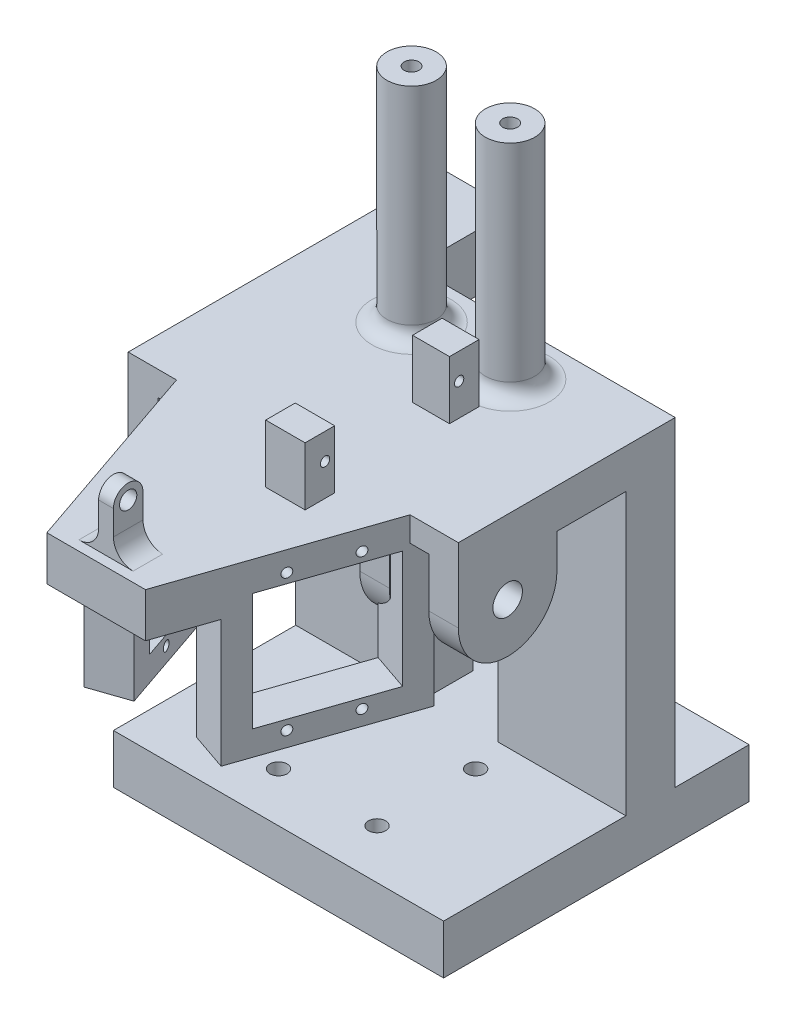
SolidWorks part; units mm, degrees
ref_plane "前视基准面" through (0, 0, 0) normal (0, 0, 1) x (1, 0, 0)
ref_plane "上视基准面" through (0, 0, 0) normal (0, 1, 0) x (1, 0, 0)
ref_plane "右视基准面" through (0, 0, 0) normal (1, 0, 0) x (0, 0, -1)
sketch "草图1" plane through (0, 0, 0) normal (0, 1, 0) x (1, 0, 0)
  line L1 (-33.5, 31) -> (33.5, 31)
  line L2 (-33.5, 31) -> (-33.5, -31)
  line L3 (-33.5, -31) -> (33.5, -31)
  line L4 (33.5, 31) -> (33.5, -31)
  line L5 (-33.5, 31) -> (33.5, -31) construction
  line L6 (-33.5, -31) -> (33.5, 31) construction
  point P0 (0, 0)
  dimension "D1" = 62
  dimension "D2" = 67
extrude "凸台-拉伸1" add sketch "草图1" along normal blind 10
sketch "草图3" plane through (0, 10, 0) normal (0, 1, 0) x (1, 0, 0)
  line L0 (-33.5, 31) -> (-33.5, -31) construction
  line L1 (-33.5, 36) -> (-19.5, 36)
  line L2 (-33.5, 36) -> (-33.5, 16)
  line L3 (-33.5, 16) -> (-19.5, 16)
  line L4 (-19.5, 36) -> (-19.5, 16)
  line L5 (33.5, 31) -> (-33.5, 31) construction
  dimension "D1" = 20
  dimension "D2" = 5
  dimension "D3" = 19.5
extrude "凸台-拉伸2" add sketch "草图3" along normal blind 12.5
sketch "草图4" plane through (-33.5, 0, 0) normal (-1, 0, 0) x (0, 0, 1)
  line L1 (-16, 10) -> (-6, 10)
  line L2 (-16, 10) -> (-16, 75)
  line L3 (-16, 75) -> (-6, 75)
  line L4 (-6, 10) -> (-6, 75)
  dimension "D1" = 10
  dimension "D2" = 65
extrude "凸台-拉伸3" add sketch "草图4" against normal blind 67
sketch "草图5" plane through (0, 75, 0) normal (0, 1, 0) x (1, 0, 0)
  line L0 (33.5, -31) -> (33.5, 6) construction
  line L1 (-33.5, 16) -> (33.5, 16)
  line L2 (-33.5, 16) -> (-33.5, -28)
  line L3 (-33.5, -28) -> (33.5, -28)
  line L4 (33.5, 16) -> (33.5, -28)
  dimension "D1" = 44
extrude "凸台-拉伸4" add sketch "草图5" against normal blind 8
sketch "草图6" plane through (33.5, 0, 0) normal (1, 0, 0) x (0, 0, -1)
  line L0 (6, 10) -> (6, 67) construction
  line L1 (-28, 75) -> (16, 75) construction
  line L2 (-28, 60) -> (-28, 67)
  line L3 (-28, 67) -> (6, 67) construction
  line L5 (-28, 67) -> (-8, 67)
  line L6 (-8, 67) -> (-8, 60)
  arc A0 (-28, 60) -> (-8, 60) centre (-18, 60) ccw
  dimension "D1" = 24
  dimension "D2" = 15
  dimension "D3" = 20
extrude "凸台-拉伸5" add sketch "草图6" against normal blind 20
sketch "草图7" plane through (33.5, 0, 0) normal (1, 0, 0) x (0, 0, -1)
  line L0 (-28, 60) -> (-28, 70.0002)
  line L1 (-28, 60) -> (-28, 75) construction
  line L2 (-28, 70.0002) -> (-8, 70.0002)
  line L3 (-8, 70.0002) -> (-8, 60)
  arc A0 (-28, 60) -> (-8, 60) centre (-18, 60) ccw construction
  arc A1 (-28, 60) -> (-8, 60) centre (-18, 60) ccw
extrude "切除-拉伸1" cut sketch "草图7" against normal blind 8 from offset 6 offset against normal yes
sketch "草图8" plane through (0, 75, 0) normal (0, 1, 0) x (1, 0, 0)
  line L0 (0, -68) -> (10, -68)
  line L2 (10, -68) -> (23.6942, -28)
  line L3 (23.6942, -28) -> (0, -28)
  line L4 (0, -28) -> (0, -68)
  line L5 (-33.5, -28) -> (33.5, -28) construction
  dimension "D1" = 10
  dimension "D2" = 40
extrude "凸台-拉伸6" add sketch "草图8" against normal blind 6
sketch "草图9" plane through (33.5, 0, 0) normal (1, 0, 0) x (0, 0, -1)
  circle A0 centre (-18, 60) radius 3
  dimension "D1" = 6
extrude "切除-拉伸2" cut sketch "草图9" against normal blind 23
sketch "草图10" plane through (29.7887, 0, 10.1983) normal (0.9461, 0, 0.3239) x (0.3239, 0, -0.9461)
  line L1 (-44, 75) -> (-15, 75)
  line L4 (-15, 75) -> (-15, 40.2)
  line L5 (-15, 40.2) -> (-43, 40.2)
  line L9 (-44, 45.2) -> (-20, 45.2)
  line L10 (-20, 45.2) -> (-20, 69)
  line L11 (-20, 69) -> (-44, 69)
  line L12 (-61.0952, 75) -> (-18.816, 75) construction
  line L14 (-44, 75) -> (-49, 75)
  line L15 (-61.0952, 75) -> (-18.816, 75) construction
  line L16 (-44, 69) -> (-44, 45.2)
  line L17 (-43, 40.2) -> (-49, 40.2)
  line L18 (-49, 75) -> (-49, 40.2)
  dimension "D1" = 5
  dimension "D2" = 5
  dimension "D3" = 29
  dimension "D4" = 15
  dimension "D5" = 24
  dimension "D6" = 28
  dimension "D7" = 5
  dimension "D8" = 6
  dimension "D9" = 23.8
extrude "凸台-拉伸7" add sketch "草图10" against normal blind 8
sketch "草图12" plane through (0, 75, 0) normal (0, 1, 0) x (1, 0, 0)
  line L1 (-33.5, 36) -> (-19.5, 36)
  line L2 (-33.5, 36) -> (-33.5, 16)
  line L3 (-33.5, 16) -> (-19.5, 16)
  line L4 (-19.5, 36) -> (-19.5, 16)
extrude "凸台-拉伸8" add sketch "草图12" against normal blind 11.5
sketch "草图13" plane through (22.22, 0, 7.6071) normal (-0.9461, 0, -0.3239) x (-0.3239, 0, 0.9461)
  line L0 (61.0952, 69) -> (49, 69) construction
  line L7 (20, 69) -> (20, 45.2) construction
  line L8 (20, 45.2) -> (44, 45.2) construction
  circle A0 centre (38.5, 70.95) radius 0.95
  circle A1 centre (26.5, 70.95) radius 0.95
  circle A2 centre (26.5, 43.25) radius 0.95
  circle A3 centre (38.5, 43.25) radius 0.95
  dimension "D2" = 6.5
  dimension "D3" = 1.95
  dimension "D4" = 1.95
  dimension "D5" = 12
  dimension "D6" = 1.9
  dimension "D7" = 1.9
  dimension "D13" = 1.9
  dimension "D14" = 1.9
extrude "切除-拉伸4" cut sketch "草图13" against normal up to surface (8 mm away) up to face at (18.1355, 63.5501, 44.2366)
sketch "草图14" plane through (0, 75, 0) normal (0, 1, 0) x (1, 0, 0)
  line L0 (33.5, 6) -> (-33.5, 6) construction
  line L1 (4.2, -2) -> (11.7, -2)
  line L2 (4.2, -2) -> (4.2, -8)
  line L3 (4.2, -8) -> (11.7, -8)
  line L4 (11.7, -2) -> (11.7, -8)
  line L5 (12.2, -31.8) -> (12.2, -37.8)
  line L6 (4.2, -37.8) -> (12.2, -37.8)
  line L7 (4.2, -31.8) -> (4.2, -37.8)
  line L8 (4.2, -31.8) -> (12.2, -31.8)
  dimension "D1" = 11.7
  dimension "D2" = 4.2
  dimension "D3" = 6
  dimension "D4" = 14
  dimension "D5" = 6
  dimension "D6" = 8
  dimension "D7" = 23.8
extrude "凸台-拉伸9" add sketch "草图14" along normal blind 11.8
sketch "草图15" plane through (4.2, 0, 0) normal (-1, 0, 0) x (0, 0, 1)
  line L0 (8, 86.8) -> (8, 75) construction
  line L1 (28, 75) -> (-36, 75) construction
  line L2 (31.8, 75) -> (37.8, 75) construction
  line L3 (31.8, 86.8) -> (31.8, 75) construction
  circle A0 centre (33.75, 81.5) radius 0.95
  circle A1 centre (6.05, 81.5) radius 0.95
  dimension "D1" = 1.95
  dimension "D2" = 1.95
  dimension "D3" = 1.9
  dimension "D4" = 1.9
  dimension "D5" = 6.5
  dimension "D6" = 6.5
extrude "切除-拉伸5" cut sketch "草图15" against normal blind 11.8
sketch "草图16" plane through (0, 75, 0) normal (0, 1, 0) x (1, 0, 0)
  line L1 (-1.5, -60) -> (1.5, -60)
  line L2 (-1.5, -60) -> (-1.5, -66)
  line L3 (-1.5, -66) -> (1.5, -66)
  line L4 (1.5, -60) -> (1.5, -66)
  point P4 (0, -66)
  dimension "D2" = 6
  dimension "D3" = 3
  dimension "D4" = 60
extrude "凸台-拉伸10" add sketch "草图16" along normal blind 12
fillet "圆角1" 2 edges at (0, 87, 66) (0, 87, 60) type full round first side face at (0, 79.8, 66) second side face at (0, 79.8, 60) middle face at (0, 87, 63)
sketch "草图17" plane through (-1.5, 0, 0) normal (-1, 0, 0) x (0, 0, 1)
  circle A0 centre (63, 84) radius 1.75
  arc A1 (66, 84) -> (60, 84) centre (63, 84) ccw construction
  dimension "D1" = 3.5
extrude "切除-拉伸6" cut sketch "草图17" against normal blind 7
sketch "草图18" plane through (0, 75, 0) normal (0, 1, 0) x (1, 0, 0)
  line L0 (33.5, 16) -> (-19.5, 16) construction
  circle A0 centre (10, 6) radius 5
  dimension "D1" = 10
  dimension "D2" = 10
  dimension "D3" = 10
extrude "凸台-拉伸11" add sketch "草图18" along normal blind 45
fillet "圆角2" radius 3 1 edges at (10, 75, -1)
mirror "镜向1" about plane through (0, 0, 0) normal (1, 0, 0) of "圆角2", "凸台-拉伸11", "切除-拉伸4", "凸台-拉伸7", "切除-拉伸2", "凸台-拉伸6", "切除-拉伸1", "凸台-拉伸5"
sketch "草图20" plane through (-33.5, 0, 0) normal (-1, 0, 0) x (0, 0, 1)
  line L0 (-36, 63.5) -> (-16, 63.5) construction
  line L1 (-36, 63.5) -> (-36, 75) construction
  circle A0 centre (-31, 67) radius 1.75
  circle A1 centre (-21, 67) radius 1.75
  circle A2 centre (-31, 19) radius 1.75
  circle A3 centre (-21, 19) radius 1.75
  dimension "D1" = 3.5
  dimension "D2" = 10
  dimension "D3" = 48
  dimension "D4" = 3.5
  dimension "D5" = 5
extrude "切除-拉伸7" cut sketch "草图20" against normal blind 35
sketch "草图21" plane through (0, 0, -16) normal (0, 0, -1) x (-1, 0, 0)
  line L1 (-7.5, 65) -> (7.5, 65)
  line L2 (-7.5, 65) -> (-7.5, 10)
  line L3 (-7.5, 10) -> (7.5, 10)
  line L4 (7.5, 65) -> (7.5, 10)
  line L5 (-33.5, 10) -> (19.5, 10) construction
  point P8 (0, 10)
  dimension "D1" = 15
  dimension "D2" = 55
extrude "切除-拉伸8" cut sketch "草图21" against normal blind 35
sketch "草图24" plane through (0, 10, 0) normal (0, 1, 0) x (1, 0, 0)
  line L0 (-33.5, -31) -> (33.5, -31) construction
  circle A0 centre (-10, -21) radius 1.75
  circle A1 centre (10, -21) radius 1.75
  circle A2 centre (-10, -1) radius 1.75
  circle A3 centre (10, -1) radius 1.75
  point P10 (0, -31)
  dimension "D1" = 20
  dimension "D2" = 20
  dimension "D5" = 10
  dimension "D6" = 3.5
  dimension "D7" = 10
  dimension "D3" = 20
  dimension "D4" = 20
extrude "切除-拉伸11" cut sketch "草图24" against normal blind 18
sketch "草图25" plane through (0, 120, 0) normal (0, 1, 0) x (1, 0, 0)
  circle A0 centre (10, 6) radius 1.5
  circle A1 centre (-10, 6) radius 1.5
  dimension "D1" = 3
  dimension "D2" = 3
extrude "切除-拉伸12" cut sketch "草图25" against normal blind 10
fillet "圆角3" radius 4 2 edges at (-1.5, 75, 63) (1.5, 75, 63)
sketch "草图26" plane through (0, 69, 0) normal (0, -1, 0) x (1, 0, 0)
  line L0 (-6.3489, 53.9656) -> (6.3489, 53.9656)
  line L16 (-19.5, 27.8155) -> (-19.5, 28)
  line L17 (-19.5, 28) -> (19.5, 28)
  line L18 (19.5, 28) -> (19.5, 27.8155)
  line L19 (19.5, 27.8155) -> (23.3107, 29.1202)
  line L20 (23.3107, 29.1202) -> (15.5371, 51.8263)
  line L21 (15.5371, 51.8263) -> (7.9684, 49.2352)
  line L22 (7.9684, 49.2352) -> (6.3489, 53.9656)
  line L23 (6.3489, 53.9656) -> (13.9176, 56.5568)
  line L24 (13.9176, 56.5568) -> (10, 68)
  line L25 (10, 68) -> (-10, 68)
  line L26 (-10, 68) -> (-13.9176, 56.5568)
  line L27 (-13.9176, 56.5568) -> (-6.3489, 53.9656)
  line L28 (-6.3489, 53.9656) -> (-7.9684, 49.2352)
  line L29 (-7.9684, 49.2352) -> (-15.5371, 51.8263)
  line L30 (-15.5371, 51.8263) -> (-23.3107, 29.1202)
  line L31 (-23.3107, 29.1202) -> (-19.5, 27.8155)
  line L32 (-19.5, 27.8155) -> (-19.5, 28)
  line L33 (-19.5, 28) -> (19.5, 28)
  line L34 (19.5, 28) -> (19.5, 27.8155)
  line L35 (19.5, 27.8155) -> (23.3107, 29.1202)
  line L36 (23.3107, 29.1202) -> (15.5371, 51.8263)
  line L39 (6.3489, 53.9656) -> (13.9176, 56.5568)
  line L40 (13.9176, 56.5568) -> (10, 68)
  line L41 (10, 68) -> (-10, 68)
  line L42 (-10, 68) -> (-13.9176, 56.5568)
  line L43 (-13.9176, 56.5568) -> (-6.3489, 53.9656)
  line L46 (-15.5371, 51.8263) -> (-23.3107, 29.1202)
  line L47 (-23.3107, 29.1202) -> (-19.5, 27.8155)
  line M24 (6.3489, 53.9656) -> (13.9176, 56.5568)
  line M25 (13.9176, 56.5568) -> (10, 68)
  line M26 (10, 68) -> (-10, 68)
  line M27 (-10, 68) -> (-13.9176, 56.5568)
  line M28 (-13.9176, 56.5568) -> (-6.3489, 53.9656)
  dimension "D1" = 0
extrude "凸台-拉伸12" add sketch "草图26" along normal blind 3 contours L0 M28 M24 M25 M26 M27 region at (0, 69, 60.9126)
sketch "草图27" plane through (0, 66, 0) normal (0, -1, 0) x (1, 0, 0)
  line L0 (-10, 68) -> (10, 68) construction
  line L1 (-4.95, 63.9) -> (4.95, 63.9)
  line L2 (-4.95, 63.9) -> (-4.95, 60.1)
  line L3 (-4.95, 60.1) -> (4.95, 60.1)
  line L4 (4.95, 63.9) -> (4.95, 60.1)
  line L5 (-4.95, 63.9) -> (4.95, 60.1) construction
  line L6 (-4.95, 60.1) -> (4.95, 63.9) construction
  line L8 (0, 68) -> (0, 59.3183) construction
  point P0 (0, 62)
  dimension "D1" = 3.8
  dimension "D2" = 9.9
  dimension "D3" = 4.1
extrude "凸台-拉伸13" add sketch "草图27" along normal blind 1
sketch "草图29" plane through (0, 65, 0) normal (0, -1, 0) x (1, 0, 0)
  line L0 (-10, 68) -> (10, 68) construction
  line L1 (-33.5, -31) -> (-33.5, 31) construction
  circle A0 centre (0, 62) radius 1.4
  dimension "D1" = 2.8
  dimension "D2" = 6
  dimension "D3" = 33.5
extrude "切除-拉伸13" cut sketch "草图29" against normal blind 4
